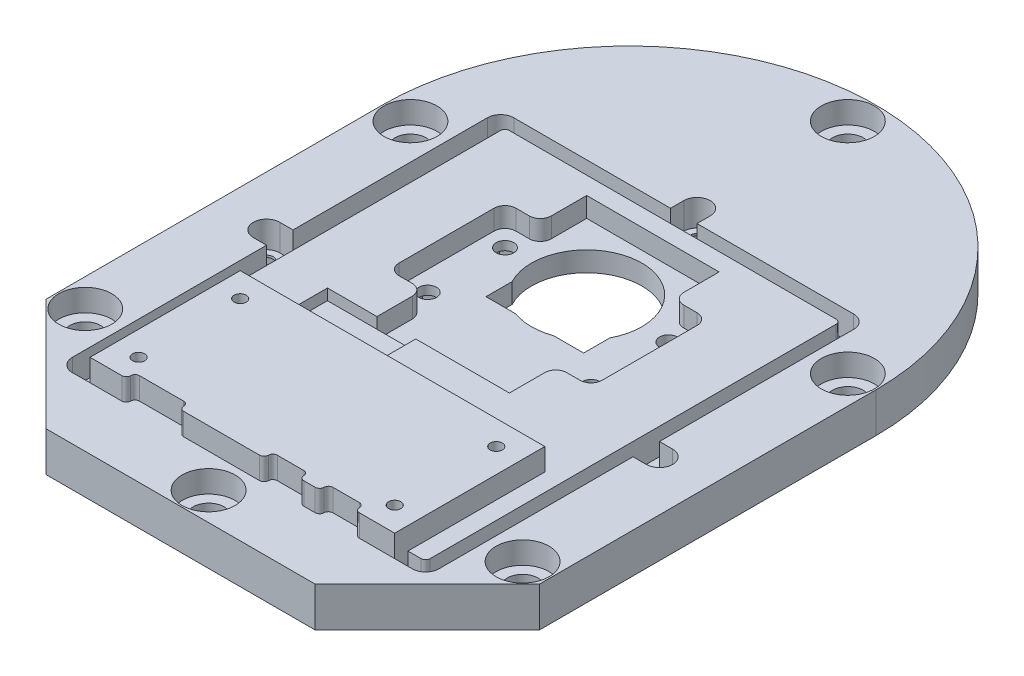
SolidWorks part; units mm, degrees
ref_plane "Alzado" through (0, 0, 0) normal (0, 0, 1) x (1, 0, 0)
ref_plane "Planta" through (0, 0, 0) normal (0, 1, 0) x (1, 0, 0)
ref_plane "Vista lateral" through (0, 0, 0) normal (1, 0, 0) x (0, 0, -1)
sketch "Croquis1" plane through (0, 0, 0) normal (0, 1, 0) x (1, 0, 0)
  line L1 (-55.88, -78.74) -> (55.88, -78.74)
  line L2 (-55.88, -78.74) -> (-55.88, 78.74)
  line L3 (-55.88, 78.74) -> (55.88, 78.74)
  line L4 (55.88, -78.74) -> (55.88, 78.74)
  line L5 (-55.88, -78.74) -> (55.88, 78.74) construction
  line L6 (-55.88, 78.74) -> (55.88, -78.74) construction
  point P0 (0, 0)
  dimension "D1" = 157.48
  dimension "D2" = 111.76
extrude "Saliente-Extruir1" add sketch "Croquis1" along normal blind 9
fillet "Redondeo1" 2 edges at (-55.88, 4.5, -78.74) (55.88, 4.5, -78.74) type full round first side face at (-55.88, 4.5, 0) second side face at (55.88, 4.5, 0) middle face at (0, 4.5, -78.74)
chamfer "Chaflán3" distance 25.4 1 edges at (-55.88, 4.5, 78.74)
chamfer "Chaflán4" distance 25.4 angle 45 1 edges at (55.88, 4.5, 78.74)
sketch "Croquis3" plane through (0, 9, 0) normal (0, 1, 0) x (1, 0, 0)
  line L0 (-30.48, -78.74) -> (30.48, -78.74) construction
  line L1 (-55.88, 22.86) -> (-55.88, -53.34) construction
  line L2 (55.88, -53.34) -> (55.88, 22.86) construction
  circle A0 centre (0, -72.39) radius 2.5
  circle A1 centre (-49.53, -50.8) radius 2.5
  circle A2 centre (49.53, -50.8) radius 2.5
  circle A3 centre (-49.53, 22.86) radius 2.5
  circle A4 centre (49.53, 22.86) radius 2.5
  circle A5 centre (0, 72.39) radius 2.5
  arc A6 (55.88, 22.86) -> (-55.88, 22.86) centre (0, 22.86) ccw construction
  point P21 (0, 78.74)
  dimension "D2" = 5
  dimension "D4" = 5
  dimension "D8" = 5
  dimension "D9" = 5
  dimension "D10" = 5
  dimension "D11" = 5
  dimension "D1" = 6.35
  dimension "D3" = 27.94
  dimension "D5" = 6.35
  dimension "D6" = 6.35
  dimension "D7" = 27.94
  dimension "D12" = 6.35
  dimension "D13" = 6.35
  dimension "D14" = 6.35
  dimension "D15" = 101.6
  dimension "D16" = 101.6
extrude "Cortar-Extruir1" cut sketch "Croquis3" against normal blind 9
sketch "Croquis14" plane through (0, 9, 0) normal (0, 1, 0) x (1, 0, 0)
  circle A0 centre (-49.53, 22.86) radius 6
  circle A1 centre (-49.53, -50.8) radius 6
  circle A2 centre (0, -72.39) radius 6
  circle A3 centre (49.53, -50.8) radius 6
  circle A4 centre (49.53, 22.86) radius 6
  circle A5 centre (0, 72.39) radius 6
  dimension "D1" = 12
  dimension "D2" = 12
  dimension "D3" = 12
  dimension "D4" = 12
  dimension "D5" = 12
  dimension "D6" = 12
extrude "Cortar-Extruir14" cut sketch "Croquis14" against normal blind 5
sketch "Croquis15" plane through (0, 4, 0) normal (0, 1, 0) x (1, 0, 0)
  circle A0 centre (49.53, -50.8) radius 3.5
  circle A1 centre (0, -72.39) radius 3.5
  circle A2 centre (-49.53, -50.8) radius 3.5
  circle A3 centre (-49.53, 22.86) radius 3.5
  circle A4 centre (49.53, 22.86) radius 3.5
  circle A5 centre (0, 72.39) radius 3.5
  dimension "D1" = 7
  dimension "D2" = 7
  dimension "D3" = 7
  dimension "D4" = 7
  dimension "D5" = 7
  dimension "D6" = 7
extrude "Cortar-Extruir15" cut sketch "Croquis15" against normal blind 5
sketch "Croquis16" plane through (0, 9, 0) normal (0, 1, 0) x (1, 0, 0)
  circle A0 centre (0, 13.24) radius 12.5
  arc A1 (55.88, 22.86) -> (-55.88, 22.86) centre (0, 22.86) ccw construction
  point P5 (0, 78.74)
  dimension "D1" = 25
  dimension "D2" = 65.5
extrude "Cortar-Extruir16" cut sketch "Croquis16" against normal blind 10
sketch "Croquis17" plane through (0, 9, 0) normal (0, 1, 0) x (1, 0, 0)
  line L0 (-33.5, -63.74) -> (33.5, -63.74)
  line L1 (-33.5, -63.74) -> (-33.5, -31.74)
  line L2 (33.5, -63.74) -> (33.5, -31.74)
  line L3 (-33.5, -31.74) -> (33.5, -31.74)
  line L4 (-33.5, -63.74) -> (33.5, -31.74) construction
  line L5 (33.5, -63.74) -> (-33.5, -31.74) construction
  line L6 (-30.48, -78.74) -> (30.48, -78.74) construction
  point P1 (0, -47.74)
  point P3 (0, -63.74)
  point P8 (0, -78.74)
  dimension "D1" = 67
  dimension "D2" = 32
  dimension "D3" = 15
  dimension "D4" = 0
extrude "Saliente-Extruir2" add sketch "Croquis17" along normal blind 5
sketch "Croquis18" plane through (0, 14, 0) normal (0, 1, 0) x (1, 0, 0)
  line L0 (33.5, -31.74) -> (-33.5, -31.74) construction
  line L2 (33.5, -63.74) -> (33.5, -31.74) construction
  line L5 (-33.5, -31.74) -> (-33.5, -63.74) construction
  circle A0 centre (29, -36.24) radius 1.375
  circle A1 centre (29, -59.24) radius 1.375
  circle A2 centre (-29, -36.24) radius 1.375
  circle A3 centre (-29, -59.24) radius 1.375
  dimension "D3" = 2.75
  dimension "D4" = 2.75
  dimension "D7" = 2.75
  dimension "D9" = 2.75
  dimension "D1" = 4.5
  dimension "D2" = 4.5
  dimension "D5" = 23
  dimension "D6" = 4.5
  dimension "D8" = 4.5
extrude "Cortar-Extruir17" cut sketch "Croquis18" against normal blind 15
sketch "Croquis21" plane through (0, 14, 0) normal (0, 1, 0) x (1, 0, 0)
  line L1 (-33.5, -63.74) -> (33.5, -63.74)
  line L2 (-33.5, -63.74) -> (-33.5, -31.74)
  line L3 (-33.5, -31.74) -> (33.5, -31.74)
  line L4 (33.5, -63.74) -> (33.5, -31.74)
  line L5 (-34.5, -64.74) -> (34.5, -64.74)
  line L6 (-34.5, -64.74) -> (-34.5, -30.74)
  line L7 (-34.5, -30.74) -> (34.5, -30.74)
  line L8 (34.5, -64.74) -> (34.5, -30.74)
  dimension "D1" = 1
  dimension "D2" = 1
  dimension "D3" = 1
  dimension "D4" = 1
extrude "Saliente-Extruir3" add sketch "Croquis21" against normal blind 5
sketch "Croquis22" plane through (0, 0, 0) normal (0, -1, 0) x (1, 0, 0)
  line L0 (34.5, 30.74) -> (-34.5, 30.74) construction
  line L1 (-32.5, 62.74) -> (32.5, 62.74)
  line L2 (-32.5, 62.74) -> (-32.5, 32.74)
  line L3 (-32.5, 32.74) -> (32.5, 32.74)
  line L4 (32.5, 62.74) -> (32.5, 32.74)
  line L5 (-30.48, 78.74) -> (30.48, 78.74) construction
  line L7 (34.5, 64.74) -> (34.5, 30.74) construction
  line L8 (-34.5, 30.74) -> (-34.5, 64.74) construction
  point P6 (0, 62.74)
  point P9 (0, 78.74)
  dimension "D1" = 30
  dimension "D2" = 2
  dimension "D3" = 65
  dimension "D4" = 0
  dimension "D5" = 2
  dimension "D6" = 2
extrude "Cortar-Extruir18" cut sketch "Croquis22" against normal blind 10
sketch "Croquis23" plane through (0, 10, 0) normal (0, -1, 0) x (1, 0, 0)
  line L1 (-29, 62.1268) -> (-31.5, 60.6834)
  line L2 (-31.5, 60.6834) -> (-31.5, 57.7966)
  line L3 (-31.5, 57.7966) -> (-29, 56.3532)
  line L4 (-29, 56.3532) -> (-26.5, 57.7966)
  line L5 (-26.5, 57.7966) -> (-26.5, 60.6834)
  line L6 (-26.5, 60.6834) -> (-29, 62.1268)
  line L7 (29, 62.1268) -> (26.5, 60.6834)
  line L8 (26.5, 60.6834) -> (26.5, 57.7966)
  line L9 (26.5, 57.7966) -> (29, 56.3532)
  line L10 (29, 56.3532) -> (31.5, 57.7966)
  line L11 (31.5, 57.7966) -> (31.5, 60.6834)
  line L12 (31.5, 60.6834) -> (29, 62.1268)
  line L13 (29, 39.1268) -> (26.5, 37.6834)
  line L14 (26.5, 37.6834) -> (26.5, 34.7966)
  line L15 (26.5, 34.7966) -> (29, 33.3532)
  line L16 (29, 33.3532) -> (31.5, 34.7966)
  line L17 (31.5, 34.7966) -> (31.5, 37.6834)
  line L18 (31.5, 37.6834) -> (29, 39.1268)
  line L19 (-29, 39.1268) -> (-31.5, 37.6834)
  line L20 (-31.5, 37.6834) -> (-31.5, 34.7966)
  line L21 (-31.5, 34.7966) -> (-29, 33.3532)
  line L22 (-29, 33.3532) -> (-26.5, 34.7966)
  line L23 (-26.5, 34.7966) -> (-26.5, 37.6834)
  line L24 (-26.5, 37.6834) -> (-29, 39.1268)
  circle A0 centre (-29, 59.24) radius 2.5 construction
  circle A1 centre (29, 59.24) radius 2.5 construction
  circle A2 centre (29, 36.24) radius 2.5 construction
  circle A3 centre (-29, 36.24) radius 2.5 construction
  dimension "D1" = 5
  dimension "D2" = 5
  dimension "D3" = 5
  dimension "D4" = 5
extrude "Cortar-Extruir19" cut sketch "Croquis23" against normal blind 2
fillet "Redondeo4" radius 3 4 edges at (32.5, 5, 32.74) (32.5, 5, 62.74) (-32.5, 5, 32.74) (-32.5, 5, 62.74)
sketch "Croquis24" plane through (0, 14, 0) normal (0, 1, 0) x (1, 0, 0)
  line L0 (-34.5, -64.74) -> (34.5, -64.74) construction
  line L1 (-26.3, -64.74) -> (-14.3, -64.74)
  line L2 (-26.3, -64.74) -> (-26.3, -62.74)
  line L3 (-26.3, -62.74) -> (-14.3, -62.74)
  line L4 (-14.3, -64.74) -> (-14.3, -62.74)
  line L5 (-29.5, -62.74) -> (29.5, -62.74) construction
  line L6 (-34.5, -30.74) -> (-34.5, -64.74) construction
  line L12 (17.5, -64.74) -> (25.5, -64.74)
  line L13 (17.5, -64.74) -> (17.5, -62.74)
  line L14 (17.5, -62.74) -> (25.5, -62.74)
  line L15 (25.5, -64.74) -> (25.5, -62.74)
  line L16 (4.9, -64.74) -> (12.9, -64.74)
  line L17 (4.9, -64.74) -> (4.9, -62.74)
  line L18 (4.9, -62.74) -> (12.9, -62.74)
  line L19 (12.9, -64.74) -> (12.9, -62.74)
  point P8 (-20.3, -64.74)
  point P19 (8.9, -64.74)
  point P20 (21.5, -64.74)
  dimension "D1" = 14.2
  dimension "D2" = 12
  dimension "D3" = 43.4
  dimension "D4" = 56
  dimension "D5" = 8
  dimension "D6" = 8
extrude "Cortar-Extruir20" cut sketch "Croquis24" against normal blind 5
sketch "Croquis25" plane through (0, 10, 0) normal (0, -1, 0) x (1, 0, 0)
  line L0 (-26.3, 62.74) -> (-29.5, 62.74) construction
  line L1 (-28.3, 62.74) -> (-12.3, 62.74)
  line L4 (-12.3, 62.74) -> (-12.3, 60.74)
  line L5 (4.9, 62.74) -> (-14.3, 62.74) construction
  line L6 (2.9, 62.74) -> (14.9, 62.74)
  line L7 (2.9, 62.74) -> (2.9, 60.74)
  line L8 (2.9, 60.74) -> (14.9, 60.74)
  line L9 (14.9, 62.74) -> (14.9, 60.74)
  line L10 (17.5, 62.74) -> (12.9, 62.74) construction
  line L11 (15.5, 62.74) -> (27.5, 62.74)
  line L12 (15.5, 62.74) -> (15.5, 60.74)
  line L15 (-28.3, 61.74) -> (-26.5981, 60.74)
  line L16 (-26.5, 60.6834) -> (-29, 62.1268) construction
  line L17 (-26.5981, 60.74) -> (-12.3, 60.74)
  line L18 (-28.3, 62.74) -> (-28.3, 61.74)
  line L19 (27.5, 62.74) -> (27.5, 61.2607)
  line L20 (29, 62.1268) -> (26.5, 60.6834) construction
  line L21 (27.5, 61.2607) -> (26.5981, 60.74)
  line L22 (26.5981, 60.74) -> (15.5, 60.74)
  dimension "D1" = 2
  dimension "D2" = 2
  dimension "D3" = 2
  dimension "D4" = 2
  dimension "D5" = 2
extrude "Saliente-Extruir4" add sketch "Croquis25" along normal blind 5
fillet "Redondeo5" radius 1 12 edges at (25.5, 11.5, 64.74) (25.5, 11.5, 62.74) (12.9, 11.5, 62.74) (17.5, 11.5, 62.74) (17.5, 11.5, 64.74) (12.9, 11.5, 64.74) (4.9, 11.5, 64.74) (4.9, 11.5, 62.74) (-14.3, 11.5, 62.74) (-14.3, 11.5, 64.74) (-26.3, 11.5, 62.74) (-26.3, 11.5, 64.74)
fillet "Redondeo6" radius 1 8 edges at (-26.5981, 7.5, 60.74) (-28.3, 7.5, 61.74) (27.5, 7.5, 61.2607) (26.5981, 7.5, 60.74) (15.5, 7.5, 60.74) (2.9, 7.5, 60.74) (14.9, 7.5, 60.74) (-12.3, 7.5, 60.74)
fillet "Redondeo12" radius 2 3 edges at (21.5, 5, 62.74) (8.9, 5, 62.74) (-20.3, 5, 62.74)
sketch "Croquis26" plane through (0, 9, 0) normal (0, 1, 0) x (1, 0, 0)
  circle A0 centre (18.5, 13.24) radius 2
  circle A1 centre (18.5, -4.26) radius 2
  circle A2 centre (-18.5, -4.26) radius 2
  circle A3 centre (-18.5, 13.24) radius 2
extrude "Cortar-Extruir21" cut sketch "Croquis26" against normal blind 10
sketch "Croquis27" plane through (0, 0, 0) normal (0, -1, 0) x (1, 0, 0)
  line L1 (-18.5524, 7.7237) -> (-21.5259, 5.9465)
  line L2 (-21.5259, 5.9465) -> (-21.4735, 2.4828)
  line L3 (-21.4735, 2.4828) -> (-18.4476, 0.7963)
  line L4 (-18.4476, 0.7963) -> (-15.4741, 2.5735)
  line L5 (-15.4741, 2.5735) -> (-15.5265, 6.0372)
  line L6 (-15.5265, 6.0372) -> (-18.5524, 7.7237)
  line L7 (-18.5524, -9.7763) -> (-21.5259, -11.5535)
  line L8 (-21.5259, -11.5535) -> (-21.4735, -15.0172)
  line L9 (-21.4735, -15.0172) -> (-18.4476, -16.7037)
  line L10 (-18.4476, -16.7037) -> (-15.4741, -14.9265)
  line L11 (-15.4741, -14.9265) -> (-15.5265, -11.4628)
  line L12 (-15.5265, -11.4628) -> (-18.5524, -9.7763)
  line L13 (18.4476, 7.7237) -> (15.4741, 5.9465)
  line L14 (15.4741, 5.9465) -> (15.5265, 2.4828)
  line L15 (15.5265, 2.4828) -> (18.5524, 0.7963)
  line L16 (18.5524, 0.7963) -> (21.5259, 2.5735)
  line L17 (21.5259, 2.5735) -> (21.4735, 6.0372)
  line L18 (21.4735, 6.0372) -> (18.4476, 7.7237)
  line L19 (18.4476, -9.7763) -> (15.4741, -11.5535)
  line L20 (15.4741, -11.5535) -> (15.5265, -15.0172)
  line L21 (15.5265, -15.0172) -> (18.5524, -16.7037)
  line L22 (18.5524, -16.7037) -> (21.5259, -14.9265)
  line L23 (21.5259, -14.9265) -> (21.4735, -11.4628)
  line L24 (21.4735, -11.4628) -> (18.4476, -9.7763)
  circle A0 centre (-18.5, 4.26) radius 3 construction
  circle A1 centre (-18.5, -13.24) radius 3 construction
  circle A2 centre (18.5, 4.26) radius 3 construction
  circle A3 centre (18.5, -13.24) radius 3 construction
  dimension "D1" = 6
  dimension "D2" = 6
  dimension "D3" = 6
  dimension "D4" = 6
extrude "Cortar-Extruir22" cut sketch "Croquis27" against normal blind 2.5
sketch "Croquis31" plane through (0, 0, 0) normal (0, -1, 0) x (1, 0, 0)
  line L0 (-9.5577, -5.24) -> (-9.5577, -2.99) construction
  line L1 (-11.0577, -8.8889) -> (11.0623, -8.8889)
  line L2 (-11.0577, -8.8889) -> (-11.0577, -1.49)
  line L3 (-11.0577, -1.49) -> (11.0623, -1.49)
  line L4 (11.0623, -8.8889) -> (11.0623, -1.49)
  line L5 (9.5623, -2.99) -> (9.5623, -5.24) construction
  line L6 (9.5623, -2.99) -> (-9.5577, -2.99) construction
  dimension "D1" = 1.5
  dimension "D2" = 1.5
  dimension "D3" = 1.5
extrude "Cortar-Extruir27" cut sketch "Croquis31" against normal blind 32
sketch "Croquis33" plane through (0, 9, 0) normal (0, 1, 0) x (1, 0, 0)
  line L0 (34.5, -64.74) -> (34.5, -30.74) construction
  line L6 (34.5, -64.74) -> (41.5, -64.74)
  line L10 (-41.5, -64.7706) -> (-34.5, -64.74)
  line L11 (-34.5, -64.74) -> (-34.5, -61.1048)
  line L12 (-34.5, -30.74) -> (-34.5, -64.74) construction
  line L13 (-34.5, -61.1048) -> (-37.5, -61.1048)
  line L14 (-37.5, -61.1048) -> (-37.5, 32.2294)
  line L15 (-37.5, 32.2294) -> (38.5, 32.2294)
  line L16 (38.5, 32.2294) -> (38.5, -61.74)
  line L17 (38.5, -61.74) -> (34.5, -61.74)
  line L18 (34.5, -61.74) -> (34.5, -64.74)
  line L19 (41.5, -64.74) -> (41.5, 35.2294)
  line L20 (-41.5, -64.7706) -> (-41.5, 35.2294)
  line L21 (-41.5, 35.2294) -> (41.5, 35.2294)
  dimension "D1" = 7
  dimension "D2" = 7
  dimension "D3" = 3
  dimension "D4" = 3
  dimension "D6" = 3
extrude "Cortar-Extruir28" cut sketch "Croquis33" against normal blind 6
sketch "Croquis35" plane through (0, 9, 0) normal (0, 1, 0) x (1, 0, 0)
  line L0 (-41.5, 35.2294) -> (-41.5, -64.7706) construction
  line L1 (-41.5, -17.7706) -> (-47.5, -17.7706)
  line L2 (-41.5, -17.7706) -> (-41.5, -11.7706)
  line L3 (-41.5, -11.7706) -> (-47.5, -11.7706)
  line L4 (-47.5, -17.7706) -> (-47.5, -11.7706)
  line L5 (41.5, -64.74) -> (41.5, 35.2294) construction
  line L6 (41.5, -17.7706) -> (47.5, -17.7706)
  line L7 (41.5, -17.7706) -> (41.5, -11.7706)
  line L8 (41.5, -11.7706) -> (47.5, -11.7706)
  line L9 (47.5, -17.7706) -> (47.5, -11.7706)
  line L10 (41.5, 35.2294) -> (-41.5, 35.2294) construction
  line L11 (-3, 35.2294) -> (3, 35.2294)
  line L12 (-3, 35.2294) -> (-3, 41.2294)
  line L13 (-3, 41.2294) -> (3, 41.2294)
  line L14 (3, 35.2294) -> (3, 41.2294)
  point P18 (-41.5, -14.7706)
  point P19 (41.5, -14.7706)
  point P20 (0, 35.2294)
  point P21 (0, 35.2294)
  dimension "D1" = 50
  dimension "D2" = 50
  dimension "D3" = 0
  dimension "D4" = 6
  dimension "D5" = 6
  dimension "D6" = 6
  dimension "D7" = 6
  dimension "D8" = 6
  dimension "D9" = 6
extrude "Cortar-Extruir31" cut sketch "Croquis35" against normal blind 6
fillet "Redondeo16" 2 edges at (-47.5, 6, 11.7706) (-47.5, 6, 17.7706) type full round first side face at (-44.5, 6, 11.7706) second side face at (-44.5, 6, 17.7706) middle face at (-47.5, 6, 14.7706)
fillet "Redondeo17" 2 edges at (-3, 6, -41.2294) (3, 6, -41.2294) type full round first side face at (-3, 6, -38.2294) second side face at (3, 6, -38.2294) middle face at (0, 6, -41.2294)
fillet "Redondeo18" 2 edges at (47.5, 6, 11.7706) (47.5, 6, 17.7706) type full round first side face at (44.5, 6, 11.7706) second side face at (44.5, 6, 17.7706) middle face at (47.5, 6, 14.7706)
sketch "Croquis36" plane through (0, 3, 0) normal (0, 1, 0) x (1, 0, 0)
  circle A0 centre (-44.5, -14.7706) radius 1.5
  circle A1 centre (0, 38.2294) radius 1.5
  circle A2 centre (44.5, -14.7706) radius 1.5
  dimension "D1" = 3
  dimension "D2" = 3
  dimension "D3" = 3
extrude "Cortar-Extruir32" cut sketch "Croquis36" against normal blind 6
sketch "Croquis38" plane through (0, 0, 0) normal (0, -1, 0) x (1, 0, 0)
  line L1 (-44.5, 18.2347) -> (-47.5, 16.5027)
  line L2 (-47.5, 16.5027) -> (-47.5, 13.0386)
  line L3 (-47.5, 13.0386) -> (-44.5, 11.3065)
  line L4 (-44.5, 11.3065) -> (-41.5, 13.0386)
  line L5 (-41.5, 13.0386) -> (-41.5, 16.5027)
  line L6 (-41.5, 16.5027) -> (-44.5, 18.2347)
  line L7 (44.5, 18.2347) -> (41.5, 16.5027)
  line L8 (41.5, 16.5027) -> (41.5, 13.0386)
  line L9 (41.5, 13.0386) -> (44.5, 11.3065)
  line L10 (44.5, 11.3065) -> (47.5, 13.0386)
  line L11 (47.5, 13.0386) -> (47.5, 16.5027)
  line L12 (47.5, 16.5027) -> (44.5, 18.2347)
  line L13 (0, -34.7653) -> (-3, -36.4973)
  line L14 (-3, -36.4973) -> (-3, -39.9614)
  line L15 (-3, -39.9614) -> (0, -41.6935)
  line L16 (0, -41.6935) -> (3, -39.9614)
  line L17 (3, -39.9614) -> (3, -36.4973)
  line L18 (3, -36.4973) -> (0, -34.7653)
  circle A0 centre (-44.5, 14.7706) radius 3 construction
  circle A1 centre (44.5, 14.7706) radius 3 construction
  circle A2 centre (0, -38.2294) radius 3 construction
  dimension "D1" = 6
  dimension "D2" = 6
  dimension "D3" = 6
extrude "Cortar-Extruir33" cut sketch "Croquis38" against normal blind 2.5
sketch "Croquis39" plane through (0, 9, 0) normal (0, 1, 0) x (1, 0, 0)
  line L0 (15, 28.24) -> (15, 20.24)
  line L1 (15, 28.24) -> (15, 20.24) construction
  line L2 (17.5, 17.74) -> (20.5, 17.74)
  line L3 (23, 15.24) -> (23, -6.26)
  line L4 (20.5, -8.76) -> (17.5, -8.76)
  line L5 (15, -11.26) -> (15, -19.26)
  line L6 (15, -19.26) -> (-15, -19.26)
  line L7 (-15, -19.26) -> (-15, -11.26)
  line L8 (-17.5, -8.76) -> (-20.5, -8.76)
  line L9 (-23, -6.26) -> (-23, 15.24)
  line L10 (-20.5, 17.74) -> (-17.5, 17.74)
  line L12 (-15, 20.24) -> (-15, 28.24) construction
  line L13 (-15, 20.24) -> (-15, 28.24)
  line L14 (-15, 28.24) -> (15, 28.24)
  arc A0 (15, 20.24) -> (17.5, 17.74) centre (17.5, 20.24) ccw construction
  arc A1 (15, 20.24) -> (17.5, 17.74) centre (17.5, 20.24) ccw
  arc A2 (23, 15.24) -> (20.5, 17.74) centre (20.5, 15.24) ccw
  arc A3 (23, 15.24) -> (20.5, 17.74) centre (20.5, 15.24) ccw construction
  arc A4 (23, -6.26) -> (20.5, -8.76) centre (20.5, -6.26) cw
  arc A5 (20.5, -8.76) -> (23, -6.26) centre (20.5, -6.26) ccw construction
  arc A6 (15, -11.26) -> (17.5, -8.76) centre (17.5, -11.26) cw
  arc A7 (17.5, -8.76) -> (15, -11.26) centre (17.5, -11.26) ccw construction
  arc A8 (-17.5, -8.76) -> (-15, -11.26) centre (-17.5, -11.26) cw
  arc A9 (-15, -11.26) -> (-17.5, -8.76) centre (-17.5, -11.26) ccw construction
  arc A10 (-20.5, -8.76) -> (-23, -6.26) centre (-20.5, -6.26) cw
  arc A11 (-23, -6.26) -> (-20.5, -8.76) centre (-20.5, -6.26) ccw construction
  arc A12 (-23, 15.24) -> (-20.5, 17.74) centre (-20.5, 15.24) cw
  arc A13 (-20.5, 17.74) -> (-23, 15.24) centre (-20.5, 15.24) ccw construction
  arc A14 (-17.5, 17.74) -> (-15, 20.24) centre (-17.5, 20.24) ccw construction
  arc A15 (-15, 20.24) -> (-17.5, 17.74) centre (-17.5, 20.24) cw
extrude "Cortar-Extruir34" cut sketch "Croquis39" against normal blind 4.5
ref_plane "Plano1" through (-15, 9, 19.26) normal (1, 0, 0) x (0, 0, -1)
sketch "Croquis41" plane through (0, 9, 0) normal (0, 1, 0) x (1, 0, 0)
  line L0 (-15, -19.26) -> (15, -19.26) construction
  line L1 (-6.211, -19.26) -> (-26.211, -19.26)
  line L2 (-6.211, -19.26) -> (-6.211, -28.26)
  line L3 (-6.211, -28.26) -> (-26.211, -28.26)
  line L4 (-26.211, -19.26) -> (-26.211, -28.26)
  dimension "D1" = 9
  dimension "D2" = 20
extrude "Cortar-Extruir35" cut sketch "Croquis41" against normal blind 2.5
fillet "Redondeo19" radius 3 4 edges at (41.5, 6, -35.2294) (41.5, 6, 64.74) (-41.5, 6, 64.7706) (-41.5, 6, -35.2294)
fillet "Redondeo20" radius 1 4 edges at (-37.5, 6, 61.1048) (-37.5, 6, -32.2294) (38.5, 6, 61.74) (38.5, 6, -32.2294)
